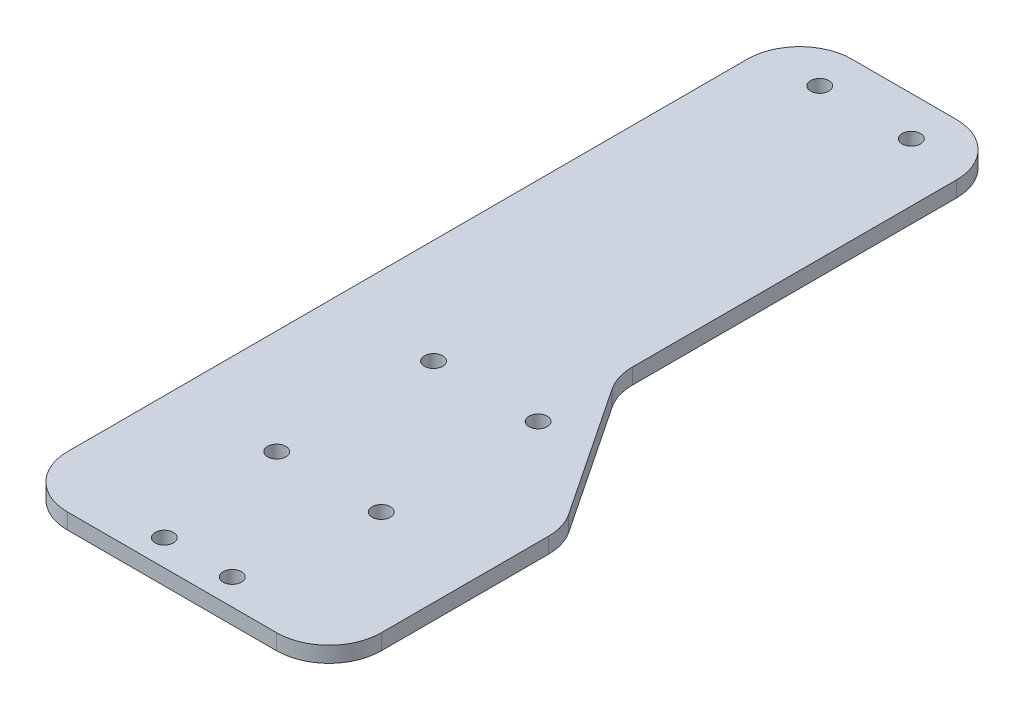
SolidWorks part; units mm, degrees
ref_plane "前视基准面" through (0, 0, 0) normal (0, 0, 1) x (1, 0, 0)
ref_plane "上视基准面" through (0, 0, 0) normal (0, 1, 0) x (1, 0, 0)
ref_plane "右视基准面" through (0, 0, 0) normal (1, 0, 0) x (0, 0, -1)
other "Configuration Table"
sketch "草图1" plane through (0, 0, 0) normal (0, 1, 0) x (1, 0, 0)
  line L0 (32.5794, -69.0423) -> (32.5794, -37.0701)
  line L1 (-17.4206, -79.0423) -> (22.5794, -79.0423)
  line L2 (-27.4206, -69.0423) -> (-27.4206, 60.9577)
  line L3 (-17.4206, 70.9577) -> (2.5794, 70.9577)
  line L4 (12.5794, -1.0146) -> (12.5794, 60.9577)
  line L7 (30.8999, -31.5231) -> (14.2589, -6.5616)
  arc A0 (14.2589, -6.5616) -> (12.5794, -1.0146) centre (22.5794, -1.0146) cw
  arc A1 (32.5794, -37.0701) -> (30.8999, -31.5231) centre (22.5794, -37.0701) ccw
  arc A2 (32.5794, -69.0423) -> (22.5794, -79.0423) centre (22.5794, -69.0423) cw
  arc A3 (-27.4206, 60.9577) -> (-17.4206, 70.9577) centre (-17.4206, 60.9577) cw
  arc A4 (-17.4206, -79.0423) -> (-27.4206, -69.0423) centre (-17.4206, -69.0423) cw
  arc A5 (2.5794, 70.9577) -> (12.5794, 60.9577) centre (2.5794, 60.9577) cw
  point P0 (0, 0)
  point P13 (12.5794, -4.0423)
  point P16 (32.5794, -34.0423)
  point P19 (32.5794, -79.0423)
  point P22 (-27.4206, 70.9577)
  point P25 (-27.4206, -79.0423)
  point P28 (12.5794, 70.9577)
  dimension "D7" = 10
  dimension "D1" = 40
  dimension "D2" = 150
  dimension "D3" = 60
  dimension "D4" = 30
  dimension "D5" = 45
extrude "凸台-拉伸1" add sketch "草图1" along normal blind 3
sketch "草图3" plane through (0, 0, 0) normal (0, -1, 0) x (1, 0, 0)
  circle A0 centre (-7.4206, 49.0423) radius 1.75
  circle A1 centre (-7.4206, 19.0423) radius 1.75
  circle A2 centre (12.5794, 19.0423) radius 1.75
  circle A3 centre (12.5794, 49.0423) radius 1.75
  circle A4 centre (-3.9206, 74.0423) radius 1.75
  circle A5 centre (9.0794, 74.0423) radius 1.75
  circle A6 centre (-16.068, -63.4577) radius 1.75
  circle A7 centre (1.4467, -63.4577) radius 1.75
  dimension "D1" = 20
  dimension "D2" = 20
extrude "切除-拉伸1" cut sketch "草图3" against normal blind 10
